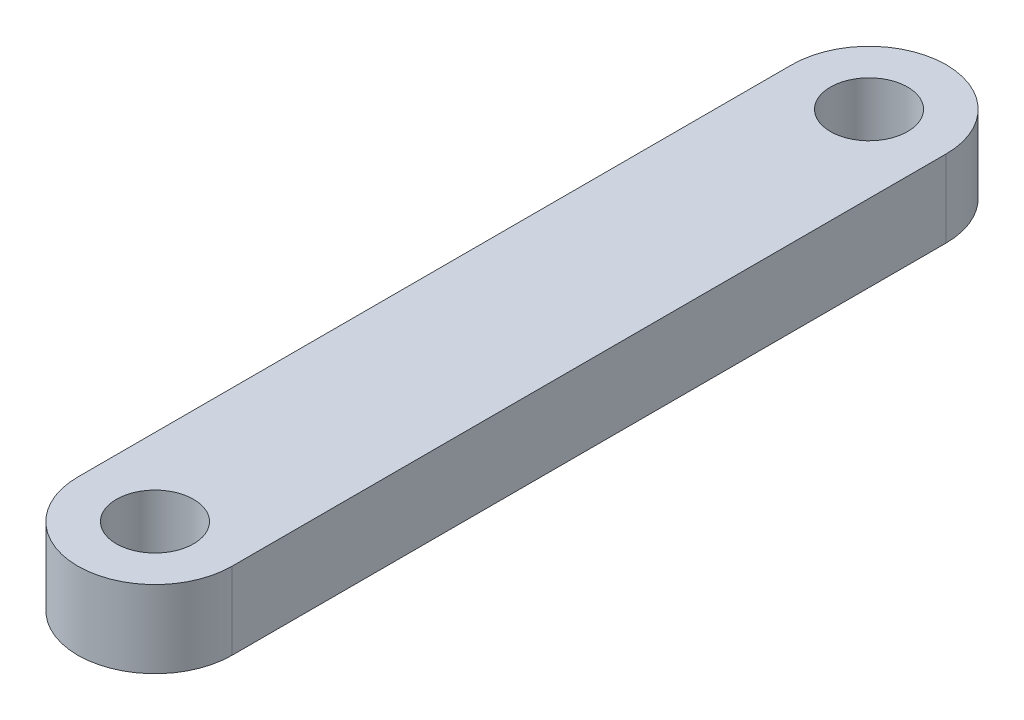
SolidWorks part; units mm, degrees
ref_plane "Front Plane" through (0, 0, 0) normal (0, 0, 1) x (1, 0, 0)
ref_plane "Top Plane" through (0, 0, 0) normal (0, 1, 0) x (1, 0, 0)
ref_plane "Right Plane" through (0, 0, 0) normal (1, 0, 0) x (0, 0, -1)
sketch "Sketch1" plane through (0, 0, 0) normal (0, 1, 0) x (1, 0, 0)
  line L0 (0, 18.5) -> (0, -18.5) construction
  line L1 (4, 18.5) -> (4, -18.5)
  line L2 (-4, 18.5) -> (-4, -18.5)
  arc A0 (4, 18.5) -> (-4, 18.5) centre (0, 18.5) ccw
  arc A1 (-4, -18.5) -> (4, -18.5) centre (0, -18.5) ccw
  circle A2 centre (0, 18.5) radius 2
  circle A3 centre (0, -18.5) radius 2
  point P2 (0, 0)
  dimension "D3" = 4
  dimension "D4" = 4
  dimension "D1" = 37
  dimension "D2" = 8
extrude "Boss-Extrude1" add sketch "Sketch1" along normal blind 4
